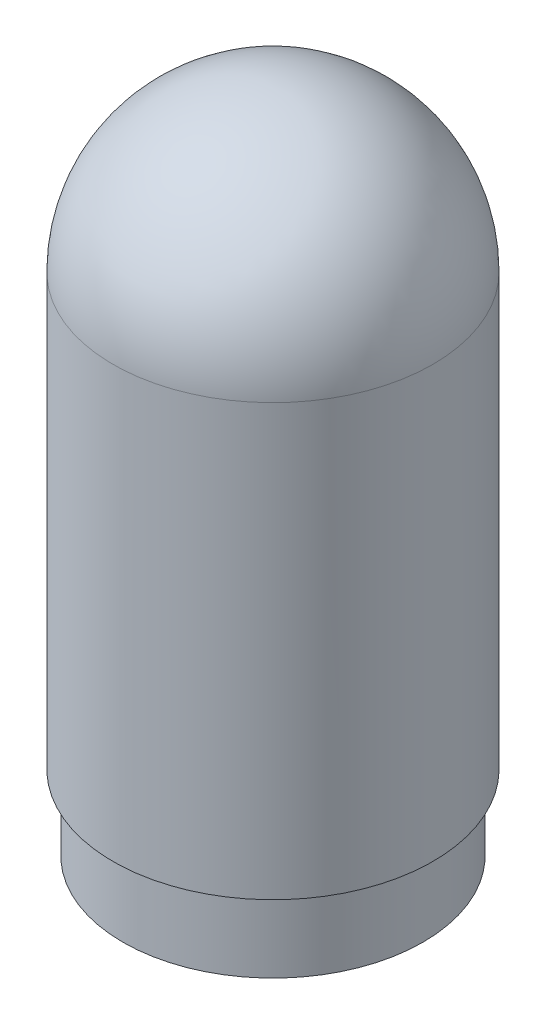
SolidWorks part; units mm, degrees
material "Acrylic (Medium-high impact)"
ref_plane "Front Plane" through (0, 0, 0) normal (0, 0, 1) x (1, 0, 0)
ref_plane "Top Plane" through (0, 0, 0) normal (0, 1, 0) x (1, 0, 0)
ref_plane "Right Plane" through (0, 0, 0) normal (1, 0, 0) x (0, 0, -1)
sketch "Sketch1" plane through (0, 0, 0) normal (0, 1, 0) x (1, 0, 0)
  circle A0 centre (0, 0) radius 30.5
  circle A1 centre (0, 0) radius 22.5
extrude "Boss-Extrude2" add sketch "Sketch1" along normal blind 15
sketch "Sketch5" plane through (0, 0, 0) normal (0, 0, 1) x (1, 0, 0)
  line L0 (0, 24.3003) -> (0, 49.0135) construction
  line L1 (0, 15.2089) -> (32.5, 15.2089)
  line L2 (32.5, 15.2089) -> (32.5, 102.7089)
  line L3 (0, 15.2089) -> (0, 135.2089)
  arc A0 (0, 135.2089) -> (32.5, 102.7089) centre (0, 102.7089) cw
  dimension "D1" = 32.5
  dimension "D2" = 120
revolve "Revolve2" add sketch "Sketch5" angle 360 about L0 other way angle 360
sketch "Sketch6" plane through (0, 0, 0) normal (0, 0, 1) x (1, 0, 0)
  line L0 (0, 102.7089) -> (0, 79.8784) construction
  line L1 (22.5, 15) -> (22.5, 102.7089)
  line L2 (22.5, 15) -> (0, 15)
  line L3 (30.5, 15) -> (-30.5, 15) construction
  line L4 (32.5, 102.7089) -> (-32.5, 102.7089) construction
  line L5 (0, 125.2089) -> (0, 15)
  arc A0 (22.5, 102.7089) -> (0, 125.2089) centre (0, 102.7089) ccw
revolve "Cut-Revolve2" cut sketch "Sketch6" angle 360 about L0
